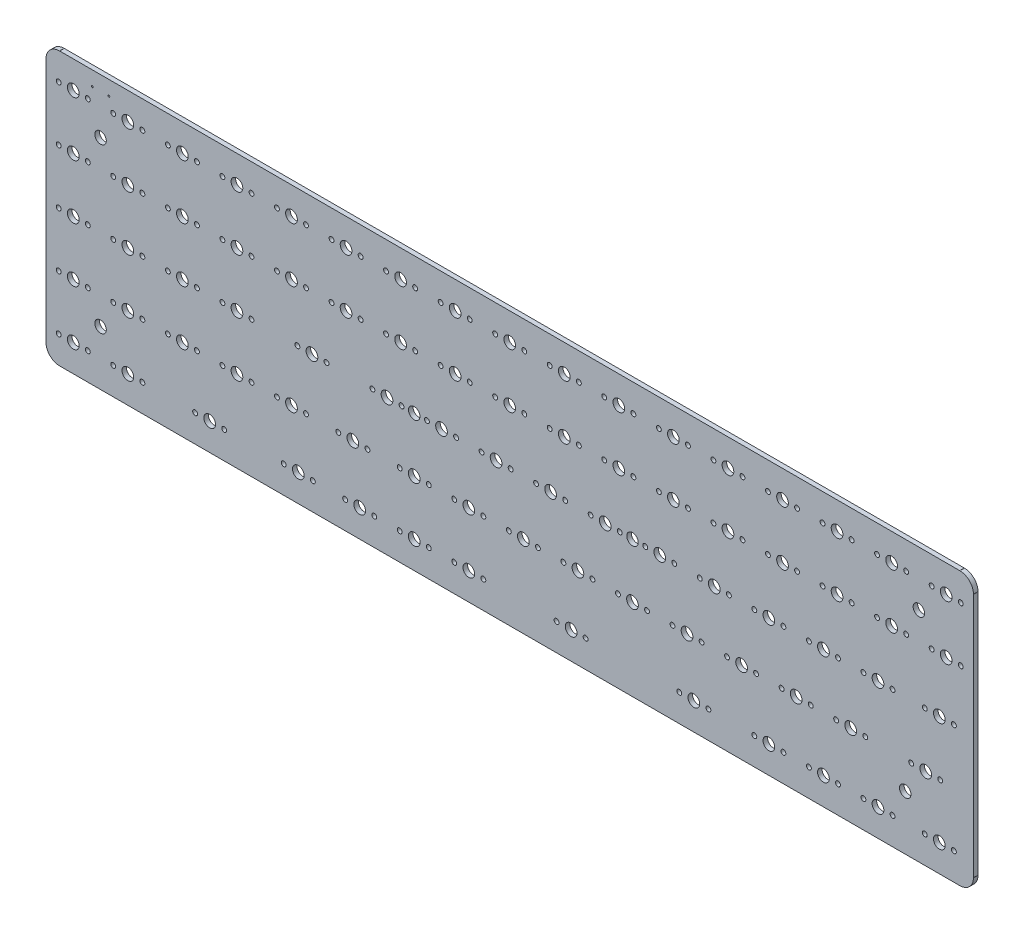
SolidWorks part; units mm, degrees
ref_plane "Front" through (0, 0, 0) normal (0, 0, 1) x (1, 0, 0)
ref_plane "Top" through (0, 0, 0) normal (0, 1, 0) x (1, 0, 0)
ref_plane "Right" through (0, 0, 0) normal (1, 0, 0) x (0, 0, -1)
sketch "Sketch2" plane through (0, 0, 0) normal (0, 0, 1) x (1, 0, 0)
  line L0 (314.325, -4.7625) -> (314.325, 80.9625)
  line L1 (309.5625, 85.725) -> (-4.7625, 85.725)
  line L2 (-9.525, 80.9625) -> (-9.525, -4.7625)
  line L3 (-4.7625, -9.525) -> (309.5625, -9.525)
  arc A0 (314.3631, 80.9625) -> (314.2869, 80.9625) centre (314.325, 80.9625) ccw
  arc A1 (314.2869, -4.7625) -> (314.3631, -4.7625) centre (314.325, -4.7625) ccw
  arc A2 (314.325, 80.9625) -> (309.5625, 85.725) centre (309.5624, 80.9624) ccw
  arc A3 (314.2869, 80.9625) -> (314.3631, 80.9625) centre (314.325, 80.9625) ccw
  arc A4 (309.5625, 85.7631) -> (309.5625, 85.6869) centre (309.5625, 85.725) ccw
  arc A5 (-4.7625, 85.7631) -> (-4.7625, 85.6869) centre (-4.7625, 85.725) ccw
  arc A6 (309.5625, 85.6869) -> (309.5625, 85.7631) centre (309.5625, 85.725) ccw
  arc A7 (-4.7625, 85.725) -> (-9.525, 80.9625) centre (-4.7624, 80.9624) ccw
  arc A8 (-4.7625, 85.6869) -> (-4.7625, 85.7631) centre (-4.7625, 85.725) ccw
  arc A9 (-9.5631, 80.9625) -> (-9.4869, 80.9625) centre (-9.525, 80.9625) ccw
  arc A10 (-9.5631, -4.7625) -> (-9.4869, -4.7625) centre (-9.525, -4.7625) ccw
  arc A11 (-9.4869, 80.9625) -> (-9.5631, 80.9625) centre (-9.525, 80.9625) ccw
  arc A12 (-9.525, -4.7625) -> (-4.7625, -9.525) centre (-4.7624, -4.7624) ccw
  arc A13 (-9.4869, -4.7625) -> (-9.5631, -4.7625) centre (-9.525, -4.7625) ccw
  arc A14 (-4.7625, -9.5631) -> (-4.7625, -9.4869) centre (-4.7625, -9.525) ccw
  arc A15 (309.5625, -9.5631) -> (309.5625, -9.4869) centre (309.5625, -9.525) ccw
  arc A16 (-4.7625, -9.4869) -> (-4.7625, -9.5631) centre (-4.7625, -9.525) ccw
  arc A17 (309.5625, -9.525) -> (314.325, -4.7625) centre (309.5624, -4.7624) ccw
  arc A18 (309.5625, -9.4869) -> (309.5625, -9.5631) centre (309.5625, -9.525) ccw
  arc A19 (314.3631, -4.7625) -> (314.2869, -4.7625) centre (314.325, -4.7625) ccw
  circle A20 centre (9.525, 66.675) radius 2
  circle A21 centre (9.525, 9.525) radius 2
  circle A22 centre (295.275, 66.675) radius 2
  circle A23 centre (290.5125, 9.525) radius 2
  circle A24 centre (119.0625, 38.1) radius 2
  circle A25 centre (195.2625, 38.1) radius 2
  circle A26 centre (304.8, 76.2) radius 2.0447
  circle A27 centre (299.72, 76.2) radius 0.8534
  circle A28 centre (309.88, 76.2) radius 0.8534
  circle A29 centre (285.75, 76.2) radius 2.0447
  circle A30 centre (280.67, 76.2) radius 0.8534
  circle A31 centre (290.83, 76.2) radius 0.8534
  circle A32 centre (266.7, 76.2) radius 2.0447
  circle A33 centre (261.62, 76.2) radius 0.8534
  circle A34 centre (271.78, 76.2) radius 0.8534
  circle A35 centre (247.65, 76.2) radius 2.0447
  circle A36 centre (242.57, 76.2) radius 0.8534
  circle A37 centre (252.73, 76.2) radius 0.8534
  circle A38 centre (228.6, 76.2) radius 2.0447
  circle A39 centre (223.52, 76.2) radius 0.8534
  circle A40 centre (233.68, 76.2) radius 0.8534
  circle A41 centre (209.55, 76.2) radius 2.0447
  circle A42 centre (204.47, 76.2) radius 0.8534
  circle A43 centre (214.63, 76.2) radius 0.8534
  circle A44 centre (190.5, 76.2) radius 2.0447
  circle A45 centre (185.42, 76.2) radius 0.8534
  circle A46 centre (195.58, 76.2) radius 0.8534
  circle A47 centre (171.45, 76.2) radius 2.0447
  circle A48 centre (166.37, 76.2) radius 0.8534
  circle A49 centre (176.53, 76.2) radius 0.8534
  circle A50 centre (152.4, 76.2) radius 2.0447
  circle A51 centre (147.32, 76.2) radius 0.8534
  circle A52 centre (157.48, 76.2) radius 0.8534
  circle A53 centre (133.35, 76.2) radius 2.0447
  circle A54 centre (128.27, 76.2) radius 0.8534
  circle A55 centre (138.43, 76.2) radius 0.8534
  circle A56 centre (114.3, 76.2) radius 2.0447
  circle A57 centre (109.22, 76.2) radius 0.8534
  circle A58 centre (119.38, 76.2) radius 0.8534
  circle A59 centre (95.25, 76.2) radius 2.0447
  circle A60 centre (90.17, 76.2) radius 0.8534
  circle A61 centre (100.33, 76.2) radius 0.8534
  circle A62 centre (76.2, 76.2) radius 2.0447
  circle A63 centre (71.12, 76.2) radius 0.8534
  circle A64 centre (81.28, 76.2) radius 0.8534
  circle A65 centre (57.15, 76.2) radius 2.0447
  circle A66 centre (52.07, 76.2) radius 0.8534
  circle A67 centre (62.23, 76.2) radius 0.8534
  circle A68 centre (38.1, 76.2) radius 2.0447
  circle A69 centre (33.02, 76.2) radius 0.8534
  circle A70 centre (43.18, 76.2) radius 0.8534
  circle A71 centre (19.05, 76.2) radius 2.0447
  circle A72 centre (13.97, 76.2) radius 0.8534
  circle A73 centre (24.13, 76.2) radius 0.8534
  circle A74 centre (0, 76.2) radius 2.0447
  circle A75 centre (-5.08, 76.2) radius 0.8534
  circle A76 centre (5.08, 76.2) radius 0.8534
  circle A77 centre (304.8, 57.15) radius 2.0447
  circle A78 centre (299.72, 57.15) radius 0.8534
  circle A79 centre (309.88, 57.15) radius 0.8534
  circle A80 centre (285.75, 57.15) radius 2.0447
  circle A81 centre (280.67, 57.15) radius 0.8534
  circle A82 centre (290.83, 57.15) radius 0.8534
  circle A83 centre (266.7, 57.15) radius 2.0447
  circle A84 centre (261.62, 57.15) radius 0.8534
  circle A85 centre (271.78, 57.15) radius 0.8534
  circle A86 centre (247.65, 57.15) radius 2.0447
  circle A87 centre (242.57, 57.15) radius 0.8534
  circle A88 centre (252.73, 57.15) radius 0.8534
  circle A89 centre (228.6, 57.15) radius 2.0447
  circle A90 centre (223.52, 57.15) radius 0.8534
  circle A91 centre (233.68, 57.15) radius 0.8534
  circle A92 centre (209.55, 57.15) radius 2.0447
  circle A93 centre (204.47, 57.15) radius 0.8534
  circle A94 centre (214.63, 57.15) radius 0.8534
  circle A95 centre (190.5, 57.15) radius 2.0447
  circle A96 centre (185.42, 57.15) radius 0.8534
  circle A97 centre (195.58, 57.15) radius 0.8534
  circle A98 centre (171.45, 57.15) radius 2.0447
  circle A99 centre (166.37, 57.15) radius 0.8534
  circle A100 centre (176.53, 57.15) radius 0.8534
  circle A101 centre (152.4, 57.15) radius 2.0447
  circle A102 centre (147.32, 57.15) radius 0.8534
  circle A103 centre (157.48, 57.15) radius 0.8534
  circle A104 centre (133.35, 57.15) radius 2.0447
  circle A105 centre (128.27, 57.15) radius 0.8534
  circle A106 centre (138.43, 57.15) radius 0.8534
  circle A107 centre (114.3, 57.15) radius 2.0447
  circle A108 centre (109.22, 57.15) radius 0.8534
  circle A109 centre (119.38, 57.15) radius 0.8534
  circle A110 centre (95.25, 57.15) radius 2.0447
  circle A111 centre (90.17, 57.15) radius 0.8534
  circle A112 centre (100.33, 57.15) radius 0.8534
  circle A113 centre (76.2, 57.15) radius 2.0447
  circle A114 centre (71.12, 57.15) radius 0.8534
  circle A115 centre (81.28, 57.15) radius 0.8534
  circle A116 centre (57.15, 57.15) radius 2.0447
  circle A117 centre (52.07, 57.15) radius 0.8534
  circle A118 centre (62.23, 57.15) radius 0.8534
  circle A119 centre (38.1, 57.15) radius 2.0447
  circle A120 centre (33.02, 57.15) radius 0.8534
  circle A121 centre (43.18, 57.15) radius 0.8534
  circle A122 centre (19.05, 57.15) radius 2.0447
  circle A123 centre (13.97, 57.15) radius 0.8534
  circle A124 centre (24.13, 57.15) radius 0.8534
  circle A125 centre (0, 57.15) radius 2.0447
  circle A126 centre (-5.08, 57.15) radius 0.8534
  circle A127 centre (5.08, 57.15) radius 0.8534
  circle A128 centre (302.4187, 38.1) radius 2.0447
  circle A129 centre (297.3388, 38.1) radius 0.8534
  circle A130 centre (307.4988, 38.1) radius 0.8534
  circle A131 centre (280.9875, 38.1) radius 2.0447
  circle A132 centre (275.9075, 38.1) radius 0.8534
  circle A133 centre (286.0675, 38.1) radius 0.8534
  circle A134 centre (261.9375, 38.1) radius 2.0447
  circle A135 centre (256.8575, 38.1) radius 0.8534
  circle A136 centre (267.0175, 38.1) radius 0.8534
  circle A137 centre (242.8875, 38.1) radius 2.0447
  circle A138 centre (237.8075, 38.1) radius 0.8534
  circle A139 centre (247.9675, 38.1) radius 0.8534
  circle A140 centre (223.8375, 38.1) radius 2.0447
  circle A141 centre (218.7575, 38.1) radius 0.8534
  circle A142 centre (228.9175, 38.1) radius 0.8534
  circle A143 centre (204.7875, 38.1) radius 2.0447
  circle A144 centre (199.7075, 38.1) radius 0.8534
  circle A145 centre (209.8675, 38.1) radius 0.8534
  circle A146 centre (185.7375, 38.1) radius 2.0447
  circle A147 centre (180.6575, 38.1) radius 0.8534
  circle A148 centre (190.8175, 38.1) radius 0.8534
  circle A149 centre (166.6875, 38.1) radius 2.0447
  circle A150 centre (161.6075, 38.1) radius 0.8534
  circle A151 centre (171.7675, 38.1) radius 0.8534
  circle A152 centre (147.6375, 38.1) radius 2.0447
  circle A153 centre (142.5575, 38.1) radius 0.8534
  circle A154 centre (152.7175, 38.1) radius 0.8534
  circle A155 centre (128.5875, 38.1) radius 2.0447
  circle A156 centre (123.5075, 38.1) radius 0.8534
  circle A157 centre (133.6675, 38.1) radius 0.8534
  circle A158 centre (109.5375, 38.1) radius 2.0447
  circle A159 centre (104.4575, 38.1) radius 0.8534
  circle A160 centre (114.6175, 38.1) radius 0.8534
  circle A161 centre (83.3438, 38.1) radius 2.0447
  circle A162 centre (78.2638, 38.1) radius 0.8534
  circle A163 centre (88.4237, 38.1) radius 0.8534
  circle A164 centre (57.15, 38.1) radius 2.0447
  circle A165 centre (52.07, 38.1) radius 0.8534
  circle A166 centre (62.23, 38.1) radius 0.8534
  circle A167 centre (38.1, 38.1) radius 2.0447
  circle A168 centre (33.02, 38.1) radius 0.8534
  circle A169 centre (43.18, 38.1) radius 0.8534
  circle A170 centre (19.05, 38.1) radius 2.0447
  circle A171 centre (13.97, 38.1) radius 0.8534
  circle A172 centre (24.13, 38.1) radius 0.8534
  circle A173 centre (0, 38.1) radius 2.0447
  circle A174 centre (-5.08, 38.1) radius 0.8534
  circle A175 centre (5.08, 38.1) radius 0.8534
  circle A176 centre (297.6563, 19.05) radius 2.0447
  circle A177 centre (292.5763, 19.05) radius 0.8534
  circle A178 centre (302.7363, 19.05) radius 0.8534
  circle A179 centre (271.4625, 19.05) radius 2.0447
  circle A180 centre (266.3825, 19.05) radius 0.8534
  circle A181 centre (276.5425, 19.05) radius 0.8534
  circle A182 centre (252.4125, 19.05) radius 2.0447
  circle A183 centre (247.3325, 19.05) radius 0.8534
  circle A184 centre (257.4925, 19.05) radius 0.8534
  circle A185 centre (233.3625, 19.05) radius 2.0447
  circle A186 centre (228.2825, 19.05) radius 0.8534
  circle A187 centre (238.4425, 19.05) radius 0.8534
  circle A188 centre (214.3125, 19.05) radius 2.0447
  circle A189 centre (209.2325, 19.05) radius 0.8534
  circle A190 centre (219.3925, 19.05) radius 0.8534
  circle A191 centre (195.2625, 19.05) radius 2.0447
  circle A192 centre (190.1825, 19.05) radius 0.8534
  circle A193 centre (200.3425, 19.05) radius 0.8534
  circle A194 centre (176.2125, 19.05) radius 2.0447
  circle A195 centre (171.1325, 19.05) radius 0.8534
  circle A196 centre (181.2925, 19.05) radius 0.8534
  circle A197 centre (157.1625, 19.05) radius 2.0447
  circle A198 centre (152.0825, 19.05) radius 0.8534
  circle A199 centre (162.2425, 19.05) radius 0.8534
  circle A200 centre (138.1125, 19.05) radius 2.0447
  circle A201 centre (133.0325, 19.05) radius 0.8534
  circle A202 centre (143.1925, 19.05) radius 0.8534
  circle A203 centre (119.0625, 19.05) radius 2.0447
  circle A204 centre (113.9825, 19.05) radius 0.8534
  circle A205 centre (124.1425, 19.05) radius 0.8534
  circle A206 centre (97.6313, 19.05) radius 2.0447
  circle A207 centre (92.5513, 19.05) radius 0.8534
  circle A208 centre (102.7113, 19.05) radius 0.8534
  circle A209 centre (76.2, 19.05) radius 2.0447
  circle A210 centre (71.12, 19.05) radius 0.8534
  circle A211 centre (81.28, 19.05) radius 0.8534
  circle A212 centre (57.15, 19.05) radius 2.0447
  circle A213 centre (52.07, 19.05) radius 0.8534
  circle A214 centre (62.23, 19.05) radius 0.8534
  circle A215 centre (38.1, 19.05) radius 2.0447
  circle A216 centre (33.02, 19.05) radius 0.8534
  circle A217 centre (43.18, 19.05) radius 0.8534
  circle A218 centre (19.05, 19.05) radius 2.0447
  circle A219 centre (13.97, 19.05) radius 0.8534
  circle A220 centre (24.13, 19.05) radius 0.8534
  circle A221 centre (0, 19.05) radius 2.0447
  circle A222 centre (-5.08, 19.05) radius 0.8534
  circle A223 centre (5.08, 19.05) radius 0.8534
  circle A224 centre (302.4187, 0) radius 2.0447
  circle A225 centre (297.3388, 0) radius 0.8534
  circle A226 centre (307.4988, 0) radius 0.8534
  circle A227 centre (280.9875, 0) radius 2.0447
  circle A228 centre (275.9075, 0) radius 0.8534
  circle A229 centre (286.0675, 0) radius 0.8534
  circle A230 centre (261.9375, 0) radius 2.0447
  circle A231 centre (256.8575, 0) radius 0.8534
  circle A232 centre (267.0175, 0) radius 0.8534
  circle A233 centre (242.8875, 0) radius 2.0447
  circle A234 centre (237.8075, 0) radius 0.8534
  circle A235 centre (247.9675, 0) radius 0.8534
  circle A236 centre (216.6938, 0) radius 2.0447
  circle A237 centre (211.6138, 0) radius 0.8534
  circle A238 centre (221.7738, 0) radius 0.8534
  circle A239 centre (173.8313, 0) radius 2.0447
  circle A240 centre (168.7512, 0) radius 0.8534
  circle A241 centre (178.9112, 0) radius 0.8534
  circle A242 centre (138.1125, 0) radius 2.0447
  circle A243 centre (133.0325, 0) radius 0.8534
  circle A244 centre (143.1925, 0) radius 0.8534
  circle A245 centre (119.0625, 0) radius 2.0447
  circle A246 centre (113.9825, 0) radius 0.8534
  circle A247 centre (124.1425, 0) radius 0.8534
  circle A248 centre (100.0125, 0) radius 2.0447
  circle A249 centre (94.9325, 0) radius 0.8534
  circle A250 centre (105.0925, 0) radius 0.8534
  circle A251 centre (78.5812, 0) radius 2.0447
  circle A252 centre (73.5012, 0) radius 0.8534
  circle A253 centre (83.6613, 0) radius 0.8534
  circle A254 centre (47.625, 0) radius 2.0447
  circle A255 centre (42.545, 0) radius 0.8534
  circle A256 centre (52.705, 0) radius 0.8534
  circle A257 centre (19.05, 0) radius 2.0447
  circle A258 centre (13.97, 0) radius 0.8534
  circle A259 centre (24.13, 0) radius 0.8534
  circle A260 centre (0, 0) radius 2.0447
  circle A261 centre (-5.08, 0) radius 0.8534
  circle A262 centre (5.08, 0) radius 0.8534
  circle A263 centre (12.415, 80.6463) radius 0.325
  circle A264 centre (6.635, 80.6463) radius 0.325
extrude "Boss-Extrude3" add sketch "Sketch2" along normal mid plane 1.5875 contours A19 L0 A3 A0 A2 A6 A4 L1 A8 A5 A7 A11 A9 L2 A13 A10 A12 A16 A14 L3 A18 A15 A17 A1 A264 A263 A262 A261 A260 A259 A258 A257 A256 A255 A254 A253 A252 region at (311.9111, -2.3486, 0)
ref_plane "Plane1" through (0, 38.1, 0) normal (0, 1, 0) x (1, 0, 0)
ref_plane "Plane2" through (152.4, 0, 0) normal (1, 0, 0) x (0, 0, -1)
